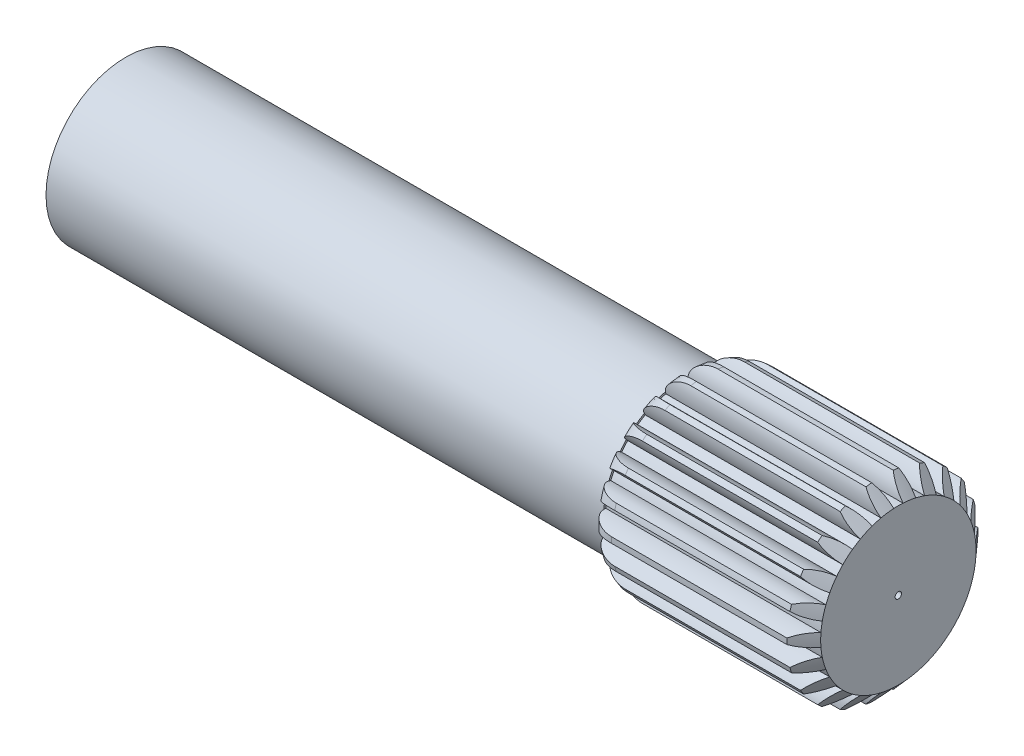
SolidWorks part; units mm, degrees
ref_plane "Plane1" through (0, 0, 0) normal (0, 0, 1) x (1, 0, 0)
ref_plane "Plane2" through (0, 0, 0) normal (0, 1, 0) x (1, 0, 0)
ref_plane "Plane3" through (0, 0, 0) normal (1, 0, 0) x (0, 0, -1)
sketch "HoldingSke" plane through (0, 0, 0) normal (0, 1, 0) x (1, 0, 0)
  line L0 (0, 0) -> (0.9272, -0.3746)
  line L1 (-15, 0) -> (100, 0) construction
  line L2 (0, 0) -> (-2.1039, 2.3779)
  line L3 (0, 0) -> (-11.863, 4.5341)
  line L4 (0, 0) -> (8.0072, 3.2351)
  line L5 (0, 0) -> (-62.7758, -23.4135)
  line L6 (0, 0) -> (-22.382, -15.1012)
  line L7 (-2.1039, 2.3779) -> (12.3178, 67.8074)
  line L8 (-76.2, 54.61) -> (-76.1, 54.61)
  line L9 (-67.7845, 28.3722) -> (-49.3413, 33.142)
  line L10 (-76.2, 71.12) -> (104.1128, 71.12)
  line L11 (0, 0) -> (-27, 0)
  line L12 (-76.2, 101.6) -> (-76.162, 101.6)
  line L13 (24.9733, 27.94) -> (52.9518, 28.4284)
  line L14 (24.9733, 27.94) -> (24.9743, 27.94)
  line L15 (24.9733, 27.94) -> (100.4006, 29.5858)
  line L16 (-63.627, -1) -> (-12.827, -1)
  circle A0 centre (0, 0) radius 0.4
  circle A1 centre (0, 0) radius 9.749
  circle A2 centre (0, 0) radius 10
  circle A3 centre (0, 0) radius 0.4
  dimension "Num_teeth" = 22
  dimension "Pitch_radius" = 180.3128
  dimension "Width" = 27
  dimension "Thickness" = 27
sketch "BasProSke" plane through (0, 0, 0) normal (0, 1, 0) x (1, 0, 0)
  line L0 (-10, 0) -> (60, 0) construction
  line L1 (0, 0) -> (0, 12)
  line L2 (0, 0) -> (27, 0)
  line L3 (27, 0) -> (27, 12)
  line L4 (27, 12) -> (0, 12)
  dimension "Thickness" = 27
  dimension "Diameter" = 24
revolve "Base-Revolve" add sketch "BasProSke" angle 360 about L0
sketch "TooCutSke" plane through (0, 0, 0) normal (1, 0, 0) x (0, 0, -1)
  line L1 (0, 0) -> (0, 107) construction
  line L2 (0, 0) -> (-0.8512, 10.967) construction
  line L3 (0, 0) -> (-3.1242, 21.7296) construction
  line L4 (-0.8512, 10.967) -> (-1.5621, 10.8648) construction
  arc A0 (0.581, 9.7317) -> (-0.581, 9.7317) centre (0, 0) ccw
  arc A1 (1.3688, 11.9472) -> (-1.3688, 11.9472) centre (0, 0) ccw
  circle A2 centre (0, 0) radius 11 construction
  circle A3 centre (0, 0) radius 10.6496 construction
  arc A4 (-0.581, 9.7317) -> (-1.3688, 11.9472) centre (-4.9698, 9.4189) ccw
  arc A5 (1.3688, 11.9472) -> (0.581, 9.7317) centre (4.9698, 9.4189) ccw
extrude "ToothCut" cut sketch "TooCutSke" along normal through all
fillet "Breaks" [suppressed] radius 0.02 tangent propagation no
fillet "RootFillets" [suppressed] radius 0.251
pattern_circular "TeethCuts" count 22 every 16.364 about axis through (-10, 0, 0) along (1, 0, 0) of "ToothCut", "RootFillets", "Breaks"
sketch "HubNeaOneSke" plane through (0, 0, 0) normal (-1, 0, 0) x (0, 0, 1)
  circle A0 centre (0, 0) radius 9.749
  dimension "Diameter" = 19.498
extrude "HubNearOne" add sketch "HubNeaOneSke" along normal blind 40.0001
sketch "HubNeaBotSke" plane through (0, 0, 0) normal (-1, 0, 0) x (0, 0, 1)
  circle A0 centre (0, 0) radius 9.749
  dimension "Diameter" = 19.498
extrude "HubNearBoth" [suppressed] add sketch "HubNeaBotSke" along normal blind 20
ref_plane "FarPln" through (27, 0, 0) normal (1, 0, 0) x (0, 0, -1)
sketch "HubFarSke" plane through (27, 0, 0) normal (1, 0, 0) x (0, 0, -1)
  circle A0 centre (0, 0) radius 9.749
  dimension "Diameter" = 19.498
extrude "HubFar" [suppressed] add sketch "HubFarSke" along normal blind 20
sketch "BorSke" plane through (0, 0, 0) normal (1, 0, 0) x (0, 0, -1)
  circle A0 centre (0, 0) radius 0.4
  dimension "Diameter" = 0.8
extrude "Bore" cut sketch "BorSke" along normal mid plane 134.0001
sketch "KeySke" plane through (0, 0, 0) normal (1, 0, 0) x (0, 0, -1)
  line L0 (-0.05, 0) -> (-0.05, 0.5)
  line L1 (-0.05, 0.5) -> (0.05, 0.5)
  line L2 (0.05, 0.5) -> (0.05, 0)
  line L3 (0, 0) -> (0, 34) construction
  line L4 (-0.05, 0) -> (0.05, 0)
extrude "Keyway" [suppressed] cut sketch "KeySke" along normal mid plane 134.0001
pattern_circular "Keyway2" [suppressed] count 2 every 90 about axis through (-10, 0, 0) along (1, 0, 0) reverse direction yes
ref_plane "Plane4" through (0, 0, 0) normal (-1, 0, 0) x (0, 0, 1)
sketch "Sketch2" plane through (0, 0, 0) normal (-1, 0, 0) x (0, 0, 1)
  circle A0 centre (0, 0) radius 10
extrude "Boss-Extrude2" add sketch "Sketch2" along normal blind 70
sketch "Sketch3" plane through (0, 0, 0) normal (0, 1, 0) x (1, 0, 0)
  line L0 (25, 12) -> (27, 9.75)
  line L2 (0, 0) -> (27, 0) construction
  line L3 (0, -0.581) -> (0, 0.581) construction
  line L4 (27, -0.581) -> (27, 0.581) construction
  line L5 (27, 0) -> (27, 12) construction
  line L6 (27, 12) -> (25, 12)
  line L7 (27, 12) -> (27, 9.75)
  point P11 (27, 11.9946)
  point P14 (27, 9.3518)
  dimension "D1" = 2.25
  dimension "D2" = 12
  dimension "D3" = 2
revolve "Cut-Revolve1" cut sketch "Sketch3" angle 360 about L2
fillet "Fillet1" radius 3 22 edges at (0, 0, -12) (0, -3.3808, -11.5139) (0, -6.4877, -10.095) (0, -9.069, -7.8583) (0, -10.9156, -4.985) (0, -11.8779, -1.7078) (0, -11.8779, 1.7078) (0, -10.9156, 4.985) (0, -9.069, 7.8583) (0, -6.4877, 10.095) (0, -3.3808, 11.5139) (0, 0, 12) (0, 3.3808, 11.5139) (0, 6.4877, 10.095) (0, 9.069, 7.8583) (0, 10.9156, 4.985) (0, 11.8779, 1.7078) (0, 3.3808, -11.5139) (0, 6.4877, -10.095) (0, 9.069, -7.8583) (0, 11.8779, -1.7078) (0, 10.9156, -4.985) second distance 2 first distance on face at (12.5, 0, -11.9973) first distance on face at (12.5, -3.38, -11.5113) first distance on face at (12.5, -6.4862, -10.0928) first distance on face at (12.5, -9.067, -7.8566) first distance on face at (12.5, -10.9131, -4.9839) first distance on face at (12.5, -11.8752, -1.7074) first distance on face at (12.5, -11.8752, 1.7074) first distance on face at (12.5, -10.9131, 4.9839) first distance on face at (12.5, -9.067, 7.8566) first distance on face at (12.5, -6.4862, 10.0928) first distance on face at (12.5, -3.38, 11.5113) first distance on face at (12.5, 0, 11.9973) first distance on face at (12.5, 3.38, 11.5113) first distance on face at (12.5, 6.4862, 10.0928) first distance on face at (12.5, 9.067, 7.8566) first distance on face at (12.5, 10.9131, 4.9839) first distance on face at (12.5, 11.8752, 1.7074) first distance on face at (12.5, 3.38, -11.5113) first distance on face at (12.5, 6.4862, -10.0928) first distance on face at (12.5, 9.067, -7.8566) first distance on face at (12.5, 11.8752, -1.7074) first distance on face at (12.5, 10.9131, -4.9839)
equation "' \"Module@HoldingSke\" = 6.35"
equation "' \"Num_teeth@HoldingSke\" = 12"
equation "' \"Ap@HoldingSke\" =  20"
equation "' \"Ap@HoldingSke\" = 20"
equation "' \"Width@HoldingSke\" = 0.5 * 25.4"
equation "' \"Hub_dia@HoldingSke\"= 1 * 25.4"
equation "' \"Hub_dia@HoldingSke\" = 1 * 25.4"
equation "' \"Overall_len@HoldingSke\" = 1.0 * 25.4"
equation "' \"Bore@HoldingSke\" = 0.75 * 25.4"
equation "' \"T_dim@HoldingSke\" = 0.1 * 25.4"
equation "' \"Width@KeySke\" = 0.25 * 25.4"
equation "' \"Show_teeth@HoldingSke\" = 13"
equation "' \"Backlash@HoldingSke\" = 0.009 * 25.4"
equation "' \"Addendum_fac@HoldingSke\" = 1.0"
equation "' \"Dedendum_fac@HoldingSke\" = 1.25"
equation "' \"Dedendum_add@HoldingSke\" = 0.00005 * 25.4"
equation "' \"Clearance_fac@HoldingSke\" = 0.25"
equation "\"Pitch@HoldingSke\" = 1 / \"Module@HoldingSke\""
equation "\"Overcut_dia@TooCutSke\" = (\"Num_teeth@HoldingSke\" + 2 * \"Addendum_fac@HoldingSke\") / \"Pitch@HoldingSke\" + 0.002 * 25.4"
equation "\"Pitch_dia@TooCutSke\" = \"Num_teeth@HoldingSke\" / \"Pitch@HoldingSke\""
equation "\"Base_dia@TooCutSke\" = \"Num_teeth@HoldingSke\" / \"Pitch@HoldingSke\" * cos((\"Ap@HoldingSke\"  * 3.14159265 / 180))"
equation "\"Root_dia@TooCutSke\" = (\"Num_teeth@HoldingSke\" + 2) / \"Pitch@HoldingSke\" - 2 * (\"Addendum_fac@HoldingSke\" + \"Dedendum_fac@HoldingSke\") / \"Pitch@HoldingSke\" - \"Dedendum_add@HoldingSke\" * 2"
equation "\"Half_ang@TooCutSke\" = 180 / \"Num_teeth@HoldingSke\""
equation "\"Half_CT@TooCutSke\" = \"Num_teeth@HoldingSke\" / \"Pitch@HoldingSke\" * sin((3.14159265 / 2 / \"Num_teeth@HoldingSke\")) / 2 - 7 * \"Backlash@HoldingSke\" / 4"
equation "\"Flank_rad@TooCutSke\" = \"Num_teeth@HoldingSke\" / \"Pitch@HoldingSke\" / 5"
equation "\"Radius@RootFillets\" = \"Clearance_fac@HoldingSke\" / \"Pitch@HoldingSke\" + \"Dedendum_add@HoldingSke\""
equation "\"Break_rad@Breaks\" = 0.02 / \"Pitch@HoldingSke\""
equation "\"Thickness@HoldingSke\" = \"Width@HoldingSke\""
equation "\"OAL@HoldingSke\" = \"Thickness@HoldingSke\""
equation "\"MHD@HoldingSke\" = (\"Num_teeth@HoldingSke\" + 2) / \"Pitch@HoldingSke\" - 2 * (\"Addendum_fac@HoldingSke\" + \"Dedendum_fac@HoldingSke\")  / \"Pitch@HoldingSke\" - \"Dedendum_add@HoldingSke\" * 2"
equation "\"MBD@HoldingSke\" = (\"Num_teeth@HoldingSke\" + 2) / \"Pitch@HoldingSke\" - 2 * (\"Addendum_fac@HoldingSke\" + \"Dedendum_fac@HoldingSke\")  / \"Pitch@HoldingSke\" - \"Dedendum_add@HoldingSke\" * 2 - 0.002 * 25.4"
equation "\"MHD@HoldingSke\" = ((sgn( \"MHD@HoldingSke\" - \"Hub_dia@HoldingSke\" )-1)*( \"MHD@HoldingSke\" - \"Hub_dia@HoldingSke\" ))/-2+ \"Hub_dia@HoldingSke\""
equation "\"MBD@HoldingSke\" = ((sgn( \"MBD@HoldingSke\" - \"Bore@HoldingSke\" )-1)*( \"MBD@HoldingSke\" - \"Bore@HoldingSke\" ))/-2+ \"Bore@HoldingSke\""
equation "\"OAL@HoldingSke\" = ((sgn( \"OAL@HoldingSke\" - \"Overall_len@HoldingSke\" )+1)*( \"OAL@HoldingSke\" - \"Overall_len@HoldingSke\" ))/2 + \"Overall_len@HoldingSke\" + 0.000002 * 25.4"
equation "\"Num_teeth@TeethCuts\" = int( \"Show_teeth@HoldingSke\" ) + 1"
equation "\"Num_teeth@TeethCuts\" = ((sgn( \"Num_teeth@TeethCuts\" - \"Num_teeth@HoldingSke\" )-1)*( \"Num_teeth@TeethCuts\" - \"Num_teeth@HoldingSke\" ))/-2+ \"Num_teeth@HoldingSke\""
equation "\"Num_teeth@TeethCuts\" = ((sgn( \"Num_teeth@TeethCuts\" - 2.0)+1)*( \"Num_teeth@TeethCuts\" - 2.0))/2 +2.0"
equation "\"Angle@TeethCuts\" = 360.0 / \"Num_teeth@HoldingSke\""
equation "\"Diameter@BasProSke\" = (\"Num_teeth@HoldingSke\" + 2 * \"Addendum_fac@HoldingSke\") / \"Pitch@HoldingSke\""
equation "\"Thickness@BasProSke\"  = \"Thickness@HoldingSke\""
equation "' \"Fillet_rad@BasProSke\" =  \"Thickness@HoldingSke\" * 0.05"
equation "' \"Fillet_rad@BasProSke\" = \"Thickness@HoldingSke\" * 0.05"
equation "\"MHD@HoldingSke\" = ((sgn( \"MHD@HoldingSke\" - \"Root_dia@TooCutSke\" )-1)*( \"MHD@HoldingSke\" - \"Root_dia@TooCutSke\" ))/-2+ \"Root_dia@TooCutSke\""
equation "\"Diameter@HubNeaOneSke\" = \"MHD@HoldingSke\""
equation "\"Length@HubNearOne\" = \"OAL@HoldingSke\" - \"Thickness@BasProSke\""
equation "\"Diameter@HubNeaBotSke\" = \"MHD@HoldingSke\""
equation "\"Length@HubNearBoth\" = ( \"OAL@HoldingSke\" - \"Thickness@BasProSke\" ) / 2.0"
equation "\"Thickness@FarPln\" = \"Thickness@BasProSke\""
equation "\"Diameter@HubFarSke\" = \"MHD@HoldingSke\""
equation "\"Length@HubFar\" = ( \"OAL@HoldingSke\" - \"Thickness@BasProSke\" ) / 2.0"
equation "\"Diameter@BorSke\" = \"MBD@HoldingSke\""
equation "\"D1@Bore\" = \"OAL@HoldingSke\" * 2.0"
equation "\"D1@Keyway\" = \"OAL@HoldingSke\" * 2.0"
equation "\"Offset@KeySke\" = \"T_dim@HoldingSke\" + \"MBD@HoldingSke\" / 2.0"
